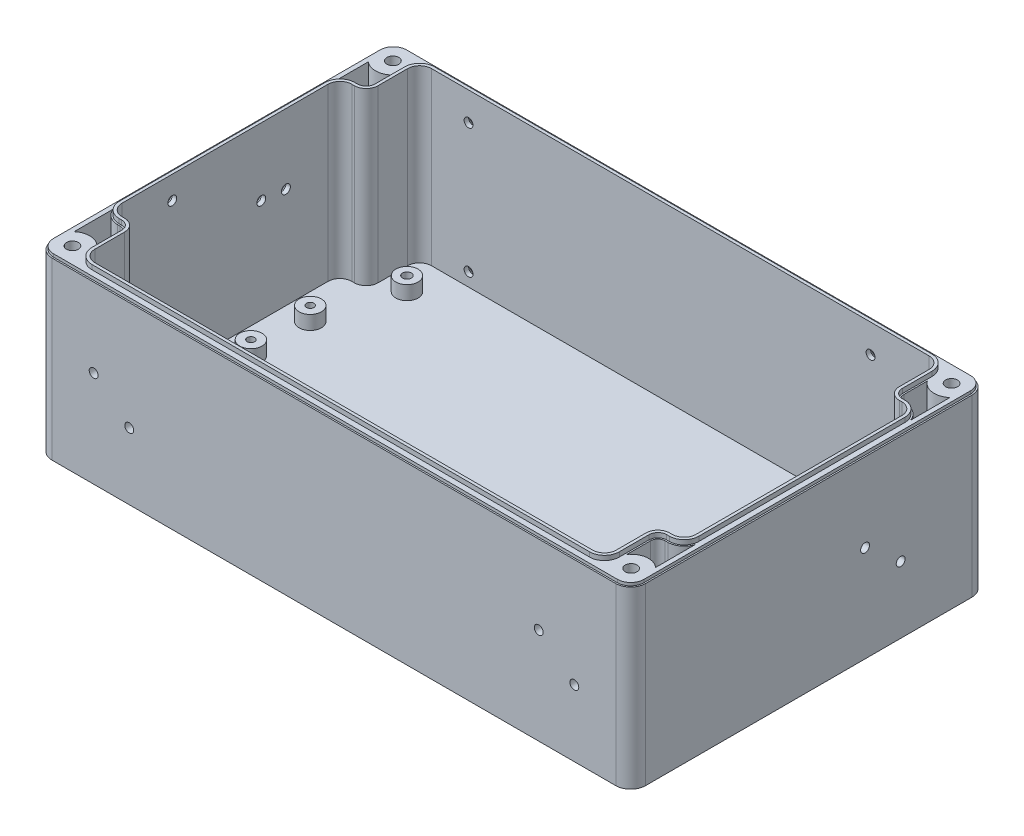
SolidWorks part; units mm, degrees
ref_plane "Front Plane" through (0, 0, 0) normal (0, 0, 1) x (1, 0, 0)
ref_plane "Top Plane" through (0, 0, 0) normal (0, 1, 0) x (1, 0, 0)
ref_plane "Right Plane" through (0, 0, 0) normal (1, 0, 0) x (0, 0, -1)
sketch "Sketch1" plane through (0, 0, 0) normal (0, 1, 0) x (1, 0, 0)
  line L1 (-100, 60) -> (100, 60)
  line L2 (-100, 60) -> (-100, -60)
  line L3 (-100, -60) -> (100, -60)
  line L4 (100, 60) -> (100, -60)
  line L5 (-100, 60) -> (100, -60) construction
  line L6 (-100, -60) -> (100, 60) construction
  point P0 (0, 0)
  dimension "D1" = 200
  dimension "D2" = 120
extrude "Boss-Extrude1" add sketch "Sketch1" along normal blind 60
fillet "Fillet1" radius 5 4 edges at (-100, 30, -60) (100, 30, -60) (100, 30, 60) (-100, 30, 60)
sketch "Sketch2" plane through (0, 60, 0) normal (0, 1, 0) x (1, 0, 0)
  line L0 (0, 60) -> (0, -60) construction
  line L1 (96.7, 56.7) -> (-96.7, 56.7)
  line L2 (96.7, 56.7) -> (96.7, -56.7)
  line L3 (96.7, -56.7) -> (-96.7, -56.7)
  line L4 (-96.7, 56.7) -> (-96.7, -56.7)
  line L5 (96.7, 56.7) -> (-96.7, -56.7) construction
  line L6 (96.7, -56.7) -> (-96.7, 56.7) construction
  line L7 (95, 60) -> (-95, 60) construction
  line L8 (-95, -60) -> (95, -60) construction
  line L9 (-100, 0) -> (99.9439, 0) construction
  line L10 (-100, 55) -> (-100, -55) construction
  line L12 (87.85, -56.7) -> (-87.85, -56.7)
  line L13 (87.85, -56.7) -> (87.85, 56.7)
  line L14 (87.85, 56.7) -> (-87.85, 56.7)
  line L15 (-87.85, -56.7) -> (-87.85, 56.7)
  line L16 (87.85, -56.7) -> (-87.85, 56.7) construction
  line L17 (87.85, 56.7) -> (-87.85, -56.7) construction
  line L18 (96.7, -38.7) -> (-96.7, -38.7)
  line L19 (96.7, -38.7) -> (96.7, 38.7)
  line L20 (96.7, 38.7) -> (-96.7, 38.7)
  line L21 (-96.7, -38.7) -> (-96.7, 38.7)
  line L22 (96.7, -38.7) -> (-96.7, 38.7) construction
  line L23 (96.7, 38.7) -> (-96.7, -38.7) construction
  circle A0 centre (-94.15, 54) radius 2
  circle A2 centre (94.15, 54) radius 2
  circle A3 centre (94.15, -54) radius 2
  circle A4 centre (-94.15, -54) radius 2
  point P0 (0, 0)
  point P18 (0, 0)
  point P19 (0, 0)
  dimension "D5" = 4
  dimension "D1" = 193.4
  dimension "D2" = 113.4
  dimension "D3" = 188.3
  dimension "D4" = 108
  dimension "D6" = 175.7
  dimension "D7" = 77.4
extrude "Cut-Extrude1" cut sketch "Sketch2" against normal offset from surface (56 mm away) 4 contours L20 L13 L1 L15 | L13 L20 L15 L18 | L13 L18 L15 L3 | L15 L20 L4 L18 | L2 L20 L13 L18 | A0 | A4 | A2 | A3 region at (0, 60, -47.7) region at (92.275, 60, 0) region at (0, 60, 0) region at (-92.275, 60, 0) region at (0, 60, 47.7) up to face at (0, 0, 0)
fillet "Fillet2" radius 4 12 edges at (87.85, 32, -56.7) (87.85, 32, -38.7) (96.7, 32, -38.7) (96.7, 32, 38.7) (87.85, 32, 38.7) (87.85, 32, 56.7) (-87.85, 32, 56.7) (-87.85, 32, 38.7) (-96.7, 32, 38.7) (-96.7, 32, -38.7) (-87.85, 32, -56.7) (-87.85, 32, -38.7)
sketch "Sketch3" plane through (0, 60, 0) normal (0, 1, 0) x (1, 0, 0)
  line L1 (83.85, 57.7) -> (-83.85, 57.7)
  line L2 (-88.85, 52.7) -> (-88.85, 42.7)
  line L3 (-91.85, 39.7) -> (-92.7, 39.7)
  line L4 (-97.7, 34.7) -> (-97.7, -34.7)
  line L5 (-92.7, -39.7) -> (-91.85, -39.7)
  line L6 (-88.85, -42.7) -> (-88.85, -52.7)
  line L7 (-83.85, -57.7) -> (83.85, -57.7)
  line L8 (88.85, -52.7) -> (88.85, -42.7)
  line L9 (91.85, -39.7) -> (92.7, -39.7)
  line L10 (97.7, -34.7) -> (97.7, 34.7)
  line L11 (92.7, 39.7) -> (91.85, 39.7)
  line L12 (88.85, 42.7) -> (88.85, 52.7)
  line L13 (87.85, 42.7) -> (87.85, 52.7)
  line L14 (92.7, 38.7) -> (91.85, 38.7)
  line L15 (96.7, -34.7) -> (96.7, 34.7)
  line L16 (91.85, -38.7) -> (92.7, -38.7)
  line L17 (87.85, -52.7) -> (87.85, -42.7)
  line L18 (-83.85, -56.7) -> (83.85, -56.7)
  line L19 (-87.85, -42.7) -> (-87.85, -52.7)
  line L20 (-92.7, -38.7) -> (-91.85, -38.7)
  line L21 (-96.7, 34.7) -> (-96.7, -34.7)
  line L22 (-91.85, 38.7) -> (-92.7, 38.7)
  line L23 (-87.85, 52.7) -> (-87.85, 42.7)
  line L24 (83.85, 56.7) -> (-83.85, 56.7)
  line L25 (87.85, 42.7) -> (87.85, 52.7)
  line L26 (92.7, 38.7) -> (91.85, 38.7)
  line L27 (96.7, -34.7) -> (96.7, 34.7)
  line L28 (91.85, -38.7) -> (92.7, -38.7)
  line L29 (87.85, -52.7) -> (87.85, -42.7)
  line L30 (-83.85, -56.7) -> (83.85, -56.7)
  line L31 (-87.85, -42.7) -> (-87.85, -52.7)
  line L32 (-92.7, -38.7) -> (-91.85, -38.7)
  line L33 (-96.7, 34.7) -> (-96.7, -34.7)
  line L34 (-91.85, 38.7) -> (-92.7, 38.7)
  line L35 (-87.85, 52.7) -> (-87.85, 42.7)
  line L36 (83.85, 56.7) -> (-83.85, 56.7)
  arc A0 (-83.85, 57.7) -> (-88.85, 52.7) centre (-83.85, 52.7) ccw
  arc A1 (-91.85, 39.7) -> (-88.85, 42.7) centre (-91.85, 42.7) ccw
  arc A2 (-92.7, 39.7) -> (-97.7, 34.7) centre (-92.7, 34.7) ccw
  arc A3 (-97.7, -34.7) -> (-92.7, -39.7) centre (-92.7, -34.7) ccw
  arc A4 (-88.85, -42.7) -> (-91.85, -39.7) centre (-91.85, -42.7) ccw
  arc A5 (-88.85, -52.7) -> (-83.85, -57.7) centre (-83.85, -52.7) ccw
  arc A6 (83.85, -57.7) -> (88.85, -52.7) centre (83.85, -52.7) ccw
  arc A7 (91.85, -39.7) -> (88.85, -42.7) centre (91.85, -42.7) ccw
  arc A8 (92.7, -39.7) -> (97.7, -34.7) centre (92.7, -34.7) ccw
  arc A9 (97.7, 34.7) -> (92.7, 39.7) centre (92.7, 34.7) ccw
  arc A10 (88.85, 42.7) -> (91.85, 39.7) centre (91.85, 42.7) ccw
  arc A11 (88.85, 52.7) -> (83.85, 57.7) centre (83.85, 52.7) ccw
  arc A12 (87.85, 42.7) -> (91.85, 38.7) centre (91.85, 42.7) ccw
  arc A13 (96.7, 34.7) -> (92.7, 38.7) centre (92.7, 34.7) ccw
  arc A14 (92.7, -38.7) -> (96.7, -34.7) centre (92.7, -34.7) ccw
  arc A15 (91.85, -38.7) -> (87.85, -42.7) centre (91.85, -42.7) ccw
  arc A16 (83.85, -56.7) -> (87.85, -52.7) centre (83.85, -52.7) ccw
  arc A17 (-87.85, -52.7) -> (-83.85, -56.7) centre (-83.85, -52.7) ccw
  arc A18 (-87.85, -42.7) -> (-91.85, -38.7) centre (-91.85, -42.7) ccw
  arc A19 (-96.7, -34.7) -> (-92.7, -38.7) centre (-92.7, -34.7) ccw
  arc A20 (-92.7, 38.7) -> (-96.7, 34.7) centre (-92.7, 34.7) ccw
  arc A21 (-91.85, 38.7) -> (-87.85, 42.7) centre (-91.85, 42.7) ccw
  arc A22 (-83.85, 56.7) -> (-87.85, 52.7) centre (-83.85, 52.7) ccw
  arc A23 (87.85, 52.7) -> (83.85, 56.7) centre (83.85, 52.7) ccw
  arc A24 (87.85, 42.7) -> (91.85, 38.7) centre (91.85, 42.7) ccw
  arc A25 (96.7, 34.7) -> (92.7, 38.7) centre (92.7, 34.7) ccw
  arc A26 (92.7, -38.7) -> (96.7, -34.7) centre (92.7, -34.7) ccw
  arc A27 (91.85, -38.7) -> (87.85, -42.7) centre (91.85, -42.7) ccw
  arc A28 (83.85, -56.7) -> (87.85, -52.7) centre (83.85, -52.7) ccw
  arc A29 (-87.85, -52.7) -> (-83.85, -56.7) centre (-83.85, -52.7) ccw
  arc A30 (-87.85, -42.7) -> (-91.85, -38.7) centre (-91.85, -42.7) ccw
  arc A31 (-96.7, -34.7) -> (-92.7, -38.7) centre (-92.7, -34.7) ccw
  arc A32 (-92.7, 38.7) -> (-96.7, 34.7) centre (-92.7, 34.7) ccw
  arc A33 (-91.85, 38.7) -> (-87.85, 42.7) centre (-91.85, 42.7) ccw
  arc A34 (-83.85, 56.7) -> (-87.85, 52.7) centre (-83.85, 52.7) ccw
  arc A35 (87.85, 52.7) -> (83.85, 56.7) centre (83.85, 52.7) ccw
  dimension "D1" = 0
  dimension "D2" = 1
extrude "Boss-Extrude2" add sketch "Sketch3" along normal blind 1.55
sketch "Sketch4" plane through (0, 4, 0) normal (0, 1, 0) x (1, 0, 0)
  circle A1 centre (-94.15, 54) radius 2
  circle A2 centre (-94.15, 54) radius 2
  circle A3 centre (94.15, 54) radius 2
  circle A4 centre (94.15, 54) radius 2
  circle A5 centre (-94.15, -54) radius 2
  circle A6 centre (-94.15, -54) radius 2
  circle A7 centre (94.15, -54) radius 2
  circle A8 centre (94.15, -54) radius 2
  dimension "D1" = 0
  dimension "D2" = 0
  dimension "D3" = 0
  dimension "D4" = 0
extrude "Cut-Extrude2" cut sketch "Sketch4" against normal up to next
sketch "Sketch5" plane through (0, 0, 0) normal (0, -1, 0) x (1, 0, 0)
  circle A0 centre (-94.15, 54) radius 3.45
  circle A1 centre (94.15, 54) radius 3.45
  circle A2 centre (94.15, -54) radius 3.45
  circle A3 centre (-94.15, -54) radius 3.45
  dimension "D1" = 6.9
extrude "Cut-Extrude3" cut sketch "Sketch5" against normal blind 52
sketch "Sketch6" plane through (0, 60, 0) normal (0, 1, 0) x (1, 0, 0)
  line L8 (95, 58) -> (-95, 58)
  line L9 (-98, 55) -> (-98, -55)
  line L10 (-95, -58) -> (95, -58)
  line L11 (98, -55) -> (98, 55)
  line L12 (95, 58) -> (-95, 58)
  line L13 (-98, 55) -> (-98, -55)
  line L14 (-95, -58) -> (95, -58)
  line L15 (98, -55) -> (98, 55)
  line L25 (-100, 55) -> (-100, -55) construction
  line L37 (83.85, 58.2) -> (-83.85, 58.2)
  line L38 (89.35, 42.7) -> (89.35, 52.7)
  line L39 (92.7, 40.2) -> (91.85, 40.2)
  line L40 (98.2, -34.7) -> (98.2, 34.7)
  line L41 (91.85, -40.2) -> (92.7, -40.2)
  line L42 (89.35, -52.7) -> (89.35, -42.7)
  line L43 (-83.85, -58.2) -> (83.85, -58.2)
  line L44 (-89.35, -42.7) -> (-89.35, -52.7)
  line L45 (-92.7, -40.2) -> (-91.85, -40.2)
  line L46 (-98.2, 34.7) -> (-98.2, -34.7)
  line L47 (-91.85, 40.2) -> (-92.7, 40.2)
  line L48 (-89.35, 52.7) -> (-89.35, 42.7)
  line L49 (83.85, 58.2) -> (-83.85, 58.2)
  line L50 (89.35, 42.7) -> (89.35, 52.7)
  line L51 (92.7, 40.2) -> (91.85, 40.2)
  line L52 (98.2, -34.7) -> (98.2, 34.7)
  line L53 (91.85, -40.2) -> (92.7, -40.2)
  line L54 (89.35, -52.7) -> (89.35, -42.7)
  line L55 (-83.85, -58.2) -> (83.85, -58.2)
  line L56 (-89.35, -42.7) -> (-89.35, -52.7)
  line L57 (-92.7, -40.2) -> (-91.85, -40.2)
  line L58 (-98.2, 34.7) -> (-98.2, -34.7)
  line L59 (-91.85, 40.2) -> (-92.7, 40.2)
  line L60 (-89.35, 52.7) -> (-89.35, 42.7)
  arc A8 (-95, 58) -> (-98, 55) centre (-95, 55) ccw
  arc A9 (-98, -55) -> (-95, -58) centre (-95, -55) ccw
  arc A10 (95, -58) -> (98, -55) centre (95, -55) ccw
  arc A11 (98, 55) -> (95, 58) centre (95, 55) ccw
  arc A12 (-95, 58) -> (-98, 55) centre (-95, 55) ccw
  arc A13 (-98, -55) -> (-95, -58) centre (-95, -55) ccw
  arc A14 (95, -58) -> (98, -55) centre (95, -55) ccw
  arc A15 (98, 55) -> (95, 58) centre (95, 55) ccw
  circle A24 centre (-94.15, 54) radius 5.85
  circle A25 centre (94.15, 54) radius 5.85
  circle A26 centre (94.15, -54) radius 5.85
  circle A27 centre (-94.15, -54) radius 5.85
  arc A36 (89.35, 52.7) -> (83.85, 58.2) centre (83.85, 52.7) ccw
  arc A37 (89.35, 42.7) -> (91.85, 40.2) centre (91.85, 42.7) ccw
  arc A38 (98.2, 34.7) -> (92.7, 40.2) centre (92.7, 34.7) ccw
  arc A39 (92.7, -40.2) -> (98.2, -34.7) centre (92.7, -34.7) ccw
  arc A40 (91.85, -40.2) -> (89.35, -42.7) centre (91.85, -42.7) ccw
  arc A41 (83.85, -58.2) -> (89.35, -52.7) centre (83.85, -52.7) ccw
  arc A42 (-89.35, -52.7) -> (-83.85, -58.2) centre (-83.85, -52.7) ccw
  arc A43 (-89.35, -42.7) -> (-91.85, -40.2) centre (-91.85, -42.7) ccw
  arc A44 (-98.2, -34.7) -> (-92.7, -40.2) centre (-92.7, -34.7) ccw
  arc A45 (-92.7, 40.2) -> (-98.2, 34.7) centre (-92.7, 34.7) ccw
  arc A46 (-91.85, 40.2) -> (-89.35, 42.7) centre (-91.85, 42.7) ccw
  arc A47 (-83.85, 58.2) -> (-89.35, 52.7) centre (-83.85, 52.7) ccw
  arc A48 (89.35, 52.7) -> (83.85, 58.2) centre (83.85, 52.7) ccw
  arc A49 (89.35, 42.7) -> (91.85, 40.2) centre (91.85, 42.7) ccw
  arc A50 (98.2, 34.7) -> (92.7, 40.2) centre (92.7, 34.7) ccw
  arc A51 (92.7, -40.2) -> (98.2, -34.7) centre (92.7, -34.7) ccw
  arc A52 (91.85, -40.2) -> (89.35, -42.7) centre (91.85, -42.7) ccw
  arc A53 (83.85, -58.2) -> (89.35, -52.7) centre (83.85, -52.7) ccw
  arc A54 (-89.35, -52.7) -> (-83.85, -58.2) centre (-83.85, -52.7) ccw
  arc A55 (-89.35, -42.7) -> (-91.85, -40.2) centre (-91.85, -42.7) ccw
  arc A56 (-98.2, -34.7) -> (-92.7, -40.2) centre (-92.7, -34.7) ccw
  arc A57 (-92.7, 40.2) -> (-98.2, 34.7) centre (-92.7, 34.7) ccw
  arc A58 (-91.85, 40.2) -> (-89.35, 42.7) centre (-91.85, 42.7) ccw
  arc A59 (-83.85, 58.2) -> (-89.35, 52.7) centre (-83.85, 52.7) ccw
  dimension "D1" = 2
  dimension "D2" = 0.5
extrude "Cut-Extrude4" cut sketch "Sketch6" against normal up to surface (56 mm away) contours L59 A58 L60 A24 L13 A57 | A50 L15 A25 L50 A49 L51 | L53 A52 L54 A26 L15 A51 | A56 L13 A27 L56 A55 L57 region at (93.8916, 60, -44.1874) region at (93.8916, 60, 44.1874) region at (-93.8916, 60, -44.1874) region at (-93.8916, 60, 44.1874) up to face at (0, 4, 0)
sketch "Sketch7" plane through (0, 0, 0) normal (0, -1, 0) x (1, 0, 0)
  line L0 (-94.15, 54) -> (-94.15, -54) construction
  line L1 (94.15, -45) -> (-94.15, -45)
  line L2 (94.15, -45) -> (94.15, 45)
  line L3 (94.15, 45) -> (-94.15, 45)
  line L4 (-94.15, -45) -> (-94.15, 45)
  line L5 (94.15, -45) -> (-94.15, 45) construction
  line L6 (94.15, 45) -> (-94.15, -45) construction
  circle A0 centre (-94.15, 45) radius 2.225
  circle A1 centre (94.15, 45) radius 2.225
  circle A2 centre (94.15, -45) radius 2.225
  circle A3 centre (-94.15, -45) radius 2.225
  point P0 (0, 0)
  dimension "D2" = 4.45
  dimension "D1" = 90
extrude "Cut-Extrude5" cut sketch "Sketch7" against normal up to next contours A0 | A1 | A2 | A3
sketch "Sketch8" plane through (0, 4, 0) normal (0, 1, 0) x (1, 0, 0)
  line L0 (0, 60) -> (0, -60) construction
  line L1 (95, 60) -> (-95, 60) construction
  line L2 (-95, -60) -> (95, -60) construction
  line L3 (-100, 0) -> (100, 0) construction
  line L4 (-100, 55) -> (-100, -55) construction
  line L5 (100, -55) -> (100, 55) construction
  line L6 (-80.4, 45) -> (80.4, 45) construction
  line L7 (-80.4, 45) -> (-80.4, -45) construction
  line L8 (-88, 60) -> (-88, -60) construction
  circle A0 centre (-80.4, 45) radius 3.75
  circle A1 centre (-80.4, 45) radius 1.5
  circle A2 centre (80.4, 45) radius 3.75
  circle A3 centre (80.4, 45) radius 1.5
  circle A4 centre (80.4, -45) radius 3.75
  circle A5 centre (80.4, -45) radius 1.5
  circle A6 centre (-80.4, -45) radius 3.75
  circle A7 centre (-80.4, -45) radius 1.5
  circle A8 centre (-57.9, 45) radius 3.75
  circle A9 centre (-57.9, 45) radius 1.25
  circle A12 centre (-57.9, -45) radius 1.25
  circle A13 centre (-57.9, -45) radius 3.75
  circle A16 centre (-88, 0) radius 3.75
  circle A17 centre (-88, 0) radius 1.25
  circle A18 centre (-88, 20) radius 3.75
  circle A19 centre (-88, 20) radius 1.25
  circle A20 centre (-88, -20) radius 1.25
  circle A21 centre (-88, -20) radius 3.75
  circle A22 centre (88, -20) radius 3.75
  circle A23 centre (88, -20) radius 1.25
  circle A24 centre (88, 0) radius 1.25
  circle A25 centre (88, 0) radius 3.75
  circle A26 centre (88, 20) radius 3.75
  circle A27 centre (88, 20) radius 1.25
  dimension "D1" = 7.5
  dimension "D2" = 3
  dimension "D5" = 2.5
  dimension "D3" = 160.8
  dimension "D4" = 90
  dimension "D6" = 22.5
  dimension "D7" = 176
  dimension "D8" = 40
extrude "Boss-Extrude3" add sketch "Sketch8" along normal blind 4.7
sketch "Sketch9" plane through (0, 60, 0) normal (0, 1, 0) x (1, 0, 0)
  line L0 (95, 59.5) -> (-95, 59.5)
  line L1 (-99.5, 55) -> (-99.5, -55)
  line L2 (-95, -59.5) -> (95, -59.5)
  line L3 (99.5, -55) -> (99.5, 55)
  line L4 (95, 60) -> (-95, 60)
  line L5 (-100, 55) -> (-100, -55)
  line L6 (-95, -60) -> (95, -60)
  line L7 (100, -55) -> (100, 55)
  line L8 (95, 60) -> (-95, 60)
  line L9 (-100, 55) -> (-100, -55)
  line L10 (-95, -60) -> (95, -60)
  line L11 (100, -55) -> (100, 55)
  arc A0 (-95, 59.5) -> (-99.5, 55) centre (-95, 55) ccw
  arc A1 (-99.5, -55) -> (-95, -59.5) centre (-95, -55) ccw
  arc A2 (95, -59.5) -> (99.5, -55) centre (95, -55) ccw
  arc A3 (99.5, 55) -> (95, 59.5) centre (95, 55) ccw
  arc A4 (-95, 60) -> (-100, 55) centre (-95, 55) ccw
  arc A5 (-100, -55) -> (-95, -60) centre (-95, -55) ccw
  arc A6 (95, -60) -> (100, -55) centre (95, -55) ccw
  arc A7 (100, 55) -> (95, 60) centre (95, 55) ccw
  arc A8 (-95, 60) -> (-100, 55) centre (-95, 55) ccw
  arc A9 (-100, -55) -> (-95, -60) centre (-95, -55) ccw
  arc A10 (95, -60) -> (100, -55) centre (95, -55) ccw
  arc A11 (100, 55) -> (95, 60) centre (95, 55) ccw
  dimension "D1" = 0
  dimension "D2" = 0.5
extrude "Cut-Extrude6" cut sketch "Sketch9" against normal blind 1
sketch "Sketch10" plane through (0, 8.7, 0) normal (0, 1, 0) x (1, 0, 0)
  circle A1 centre (-57.9, 45) radius 3.75
  circle A2 centre (-57.9, 45) radius 3.75
  dimension "D1" = 0
extrude "Cut-Extrude7" cut sketch "Sketch10" against normal up to surface (4.7 mm away) up to face at (88, 4, -23.75)
sketch "Sketch11" plane through (0, 0, -60) normal (0, 0, -1) x (-1, 0, 0)
  circle A1 centre (71.35, 52) radius 1.5 construction
  circle A2 centre (71.35, 52) radius 1.5
  circle A3 centre (-64.15, 52) radius 1.5 construction
  circle A4 centre (-64.15, 52) radius 1.5
  circle A5 centre (-64.15, 8.5) radius 1.5 construction
  circle A6 centre (-64.15, 8.5) radius 1.5
  circle A7 centre (71.35, 8.5) radius 1.5 construction
  circle A8 centre (71.35, 8.5) radius 1.5
extrude "Cut-Extrude8" cut sketch "Sketch11" against normal up to next
hole_wizard "CSK for M3 Flat Head Machine Screw1" positions "Sketch12" profile "Sketch14" countersink size "M3" standard "ANSI Metric"
sketch "Sketch12" plane through (0, 0, -60) normal (0, 0, -1) x (-1, 0, 0)
  point P0 (71.35, 52)
  point P3 (71.35, 8.5)
  point P6 (-64.15, 8.5)
  point P9 (-64.15, 52)
sketch "Sketch14" plane through (-71.35, 52, -60) normal (1, 0, 0) x (0, 1, 0)
  line L0 (0, 0) -> (0, 4.2003)
  line L1 (0, 4.2003) -> (1.5, 3.299)
  line L2 (1.5, 3.299) -> (1.5, 1.8)
  line L3 (1.5, 1.8) -> (3, 0.3)
  line L4 (3, 0.3) -> (3, 0)
  line L6 (3, 0) -> (0, 0)
  line L7 (-1.5, 1.8) -> (-3, 0.3) construction
  line L10 (0, 4.2003) -> (-1.5, 3.299) construction
  line L11 (0, -6.35) -> (0, 107.95) construction
  dimension "Hole Dia." = 3
  dimension "Hole Depth" = 3.299
  dimension "C'Sink Dia." = 6
  dimension "C'Sink Angle" = 90
  dimension "Drill Angle" = 118
  dimension "Head Clearance" = 0.3
sketch "Sketch15" plane through (-100, 0, 0) normal (-1, 0, 0) x (0, 0, 1)
  circle A0 centre (17.8, 53.8172) radius 1.5 construction
  circle A1 centre (17.8, 53.8172) radius 1.5
  circle A2 centre (-12.2, 38.8172) radius 1.5 construction
  circle A3 centre (-12.2, 38.8172) radius 1.5
  circle A4 centre (20.5, 17.0172) radius 1.8 construction
  circle A5 centre (20.5, 17.0172) radius 1.8
  circle A6 centre (-20.5, 38.0172) radius 1.8 construction
  circle A7 centre (-20.5, 38.0172) radius 1.8
  circle A8 centre (-20.5, 38.0172) radius 1.5
  circle A9 centre (20.5, 17.0172) radius 1.5
extrude "Cut-Extrude9" cut sketch "Sketch15" against normal up to next contours A8 | A3 | A1 | A9 region at (-100, 53.8172, 17.8) region at (-100, 38.8172, -12.2) region at (-100, 38.0172, -20.5) region at (-100, 17.0172, 20.5)
hole_wizard "CSK for M3 Flat Head Machine Screw2" positions "Sketch16" profile "Sketch18" countersink size "M3" standard "ANSI Metric"
sketch "Sketch16" plane through (-100, 0, 0) normal (-1, 0, 0) x (0, 0, 1)
  point P0 (-20.5, 38.0172)
  point P3 (-12.2, 38.8172)
  point P6 (17.8, 53.8172)
  point P9 (20.5, 17.0172)
sketch "Sketch18" plane through (-100, 38.0172, -20.5) normal (0, 1, 0) x (0, 0, 1)
  line L0 (0, 0) -> (0, 4.2003)
  line L1 (0, 4.2003) -> (1.5, 3.299)
  line L2 (1.5, 3.299) -> (1.5, 1.8)
  line L3 (1.5, 1.8) -> (3, 0.3)
  line L4 (3, 0.3) -> (3, 0)
  line L6 (3, 0) -> (0, 0)
  line L7 (-1.5, 1.8) -> (-3, 0.3) construction
  line L10 (0, 4.2003) -> (-1.5, 3.299) construction
  line L11 (0, -6.35) -> (0, 107.95) construction
  dimension "Hole Dia." = 3
  dimension "Hole Depth" = 3.299
  dimension "C'Sink Dia." = 6
  dimension "C'Sink Angle" = 90
  dimension "Drill Angle" = 118
  dimension "Head Clearance" = 0.3
sketch "Sketch20" plane through (0, 0, 60) normal (0, 0, 1) x (1, 0, 0)
  line L0 (-95, 0) -> (95, 0) construction
  line L1 (-100, 0) -> (-100, 59) construction
  line L2 (0, 81.508) -> (0, -38.0481) construction
  line L3 (-81, 32.45) -> (-100, 32.45) construction
  line L4 (81, 22.45) -> (100, 22.45) construction
  line L5 (100, 59) -> (100, 0) construction
  line L6 (-81, 32.45) -> (-69, 22.45) construction
  line L7 (69, 32.45) -> (81, 22.45) construction
  circle A0 centre (-81, 32.45) radius 1.5
  circle A1 centre (-69, 22.45) radius 1.5
  circle A2 centre (69, 32.45) radius 1.5
  circle A3 centre (81, 22.45) radius 1.5
  dimension "D1" = 3
  dimension "D2" = 32.45
  dimension "D3" = 19
  dimension "D4" = 12
  dimension "D5" = 10
extrude "Cut-Extrude10" cut sketch "Sketch20" against normal up to next
sketch "Sketch21" plane through (100, 0, 0) normal (1, 0, 0) x (0, 0, -1)
  line L1 (-50, 22.45) -> (55, 22.45) construction
  line L2 (-50, 23.95) -> (-50, 20.95)
  line L3 (-50, 23.95) -> (-50, 20.95)
  line L4 (55, 0) -> (55, 59) construction
  line L5 (60, 59) -> (60, 0) construction
  circle A0 centre (31, 22.45) radius 1.5
  circle A1 centre (19, 32.45) radius 1.5
  point P12 (0, 0)
  dimension "D2" = 3
  dimension "D3" = 29
  dimension "D4" = 12
  dimension "D5" = 10
  dimension "D1" = 10
extrude "Cut-Extrude11" cut sketch "Sketch21" against normal up to next contours A1 | A0
